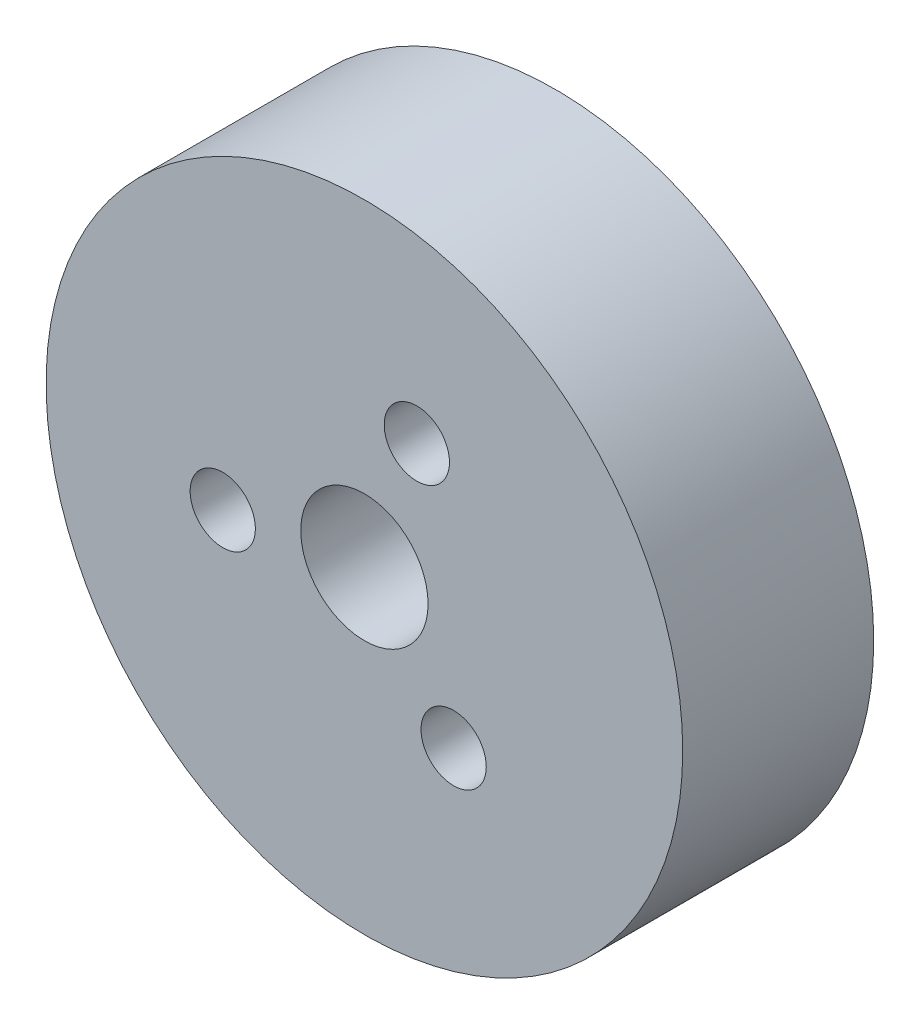
SolidWorks part; units mm, degrees
ref_plane "Front Plane" through (0, 0, 0) normal (0, 0, 1) x (1, 0, 0)
ref_plane "Top Plane" through (0, 0, 0) normal (0, 1, 0) x (1, 0, 0)
ref_plane "Right Plane" through (0, 0, 0) normal (1, 0, 0) x (0, 0, -1)
sketch "Sketch1" plane through (0, 0, 0) normal (0, 0, 1) x (1, 0, 0)
  circle A0 centre (0, 0) radius 10
  circle A1 centre (0, 0) radius 2
  dimension "D1" = 4
  dimension "D2" = 20
extrude "Boss-Extrude1" add sketch "Sketch1" along normal blind 6
hole_wizard "Ø2.05 (2.05) Diameter Hole1" positions "Sketch2" profile "Sketch3" hole size "Ø2.05" standard "ISO" end condition through all
sketch "Sketch2" plane through (-166.2191, 17.5479, 8.7955) normal (0, 0, 1) x (0.0629, -0.998, 0)
  circle A0 centre (27.9652, 164.7867) radius 4.5
  point P0 (23.8893, 166.6937)
  point P2 (31.6547, 167.3631)
  point P4 (28.3517, 160.3033)
sketch "Sketch3" plane through (1.6469, 4.1878, 8.7955) normal (1, 0, 0) x (0, -1, 0)
  line L0 (0, 0) -> (0, 8.7955)
  line L1 (0, 8.7955) -> (1.025, 8.7955)
  line L2 (1.025, 8.7955) -> (1.025, 0)
  line L3 (1.025, 0) -> (0, 0)
  line L4 (0, -6.35) -> (0, 107.95) construction
  dimension "Thru Hole Dia." = 2.05
  dimension "Thru Hole Depth" = 8.7955
